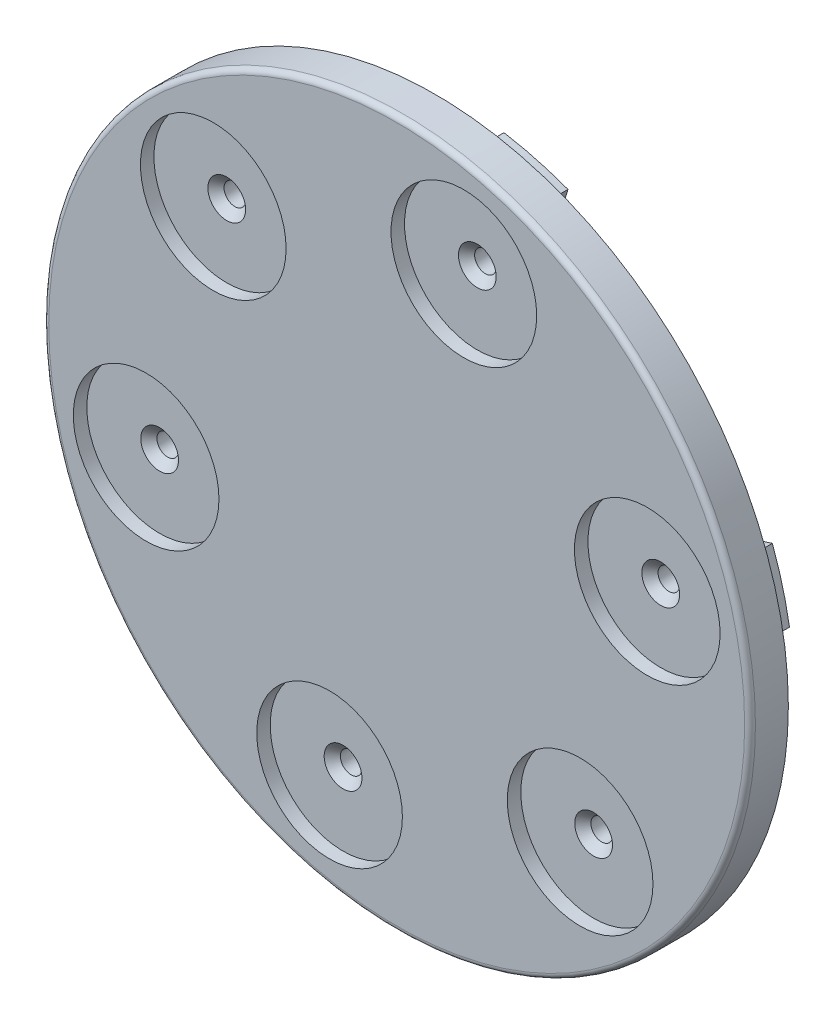
SolidWorks part; units mm, degrees
ref_plane "前视基准面" through (0, 0, 0) normal (0, 0, 1) x (1, 0, 0)
ref_plane "上视基准面" through (0, 0, 0) normal (0, 1, 0) x (1, 0, 0)
ref_plane "右视基准面" through (0, 0, 0) normal (1, 0, 0) x (0, 0, -1)
sketch "草图1" plane through (0, 0, 0) normal (0, 0, 1) x (1, 0, 0)
  line L0 (-32.5355, 8.7823) -> (-18.3435, 4.9515) construction
  line L1 (-30.451, 14.4369) -> (-16.7792, 10.7465)
  line L2 (-33.5795, 2.8469) -> (-19.9077, -0.8435)
  line L12 (10.6844, 63.6089) -> (3.9198, 33.4713)
  line L13 (-20.0302, 27.1013) -> (-41.0574, 49.7447)
  line L14 (-49.7447, 41.0574) -> (-27.0271, 20.1302)
  line L15 (-33.4855, -3.796) -> (-63.6089, -10.6844)
  line L16 (-60.4291, -22.5515) -> (-30.9468, -13.341)
  line L17 (-13.4553, -30.8973) -> (-22.5515, -60.4291)
  line L18 (-10.6844, -63.6089) -> (-3.9198, -33.4713)
  line L19 (20.0302, -27.1013) -> (41.0574, -49.7447)
  line L20 (49.7447, -41.0574) -> (27.0271, -20.1302)
  line L21 (33.4855, 3.796) -> (63.6089, 10.6844)
  line L22 (60.4291, 22.5515) -> (30.9468, 13.341)
  line L23 (13.4553, 30.8973) -> (22.5515, 60.4291)
  line L24 (10.6844, 63.6089) -> (3.9198, 33.4713)
  line L25 (-20.0302, 27.1013) -> (-41.0574, 49.7447)
  line L26 (-49.7447, 41.0574) -> (-27.0271, 20.1302)
  line L27 (-33.4855, -3.796) -> (-63.6089, -10.6844)
  line L28 (-60.4291, -22.5515) -> (-30.9468, -13.341)
  line L29 (-13.4553, -30.8973) -> (-22.5515, -60.4291)
  line L30 (-10.6844, -63.6089) -> (-3.9198, -33.4713)
  line L31 (20.0302, -27.1013) -> (41.0574, -49.7447)
  line L32 (49.7447, -41.0574) -> (27.0271, -20.1302)
  line L33 (33.4855, 3.796) -> (63.6089, 10.6844)
  line L34 (60.4291, 22.5515) -> (30.9468, 13.341)
  line L35 (13.4553, 30.8973) -> (22.5515, 60.4291)
  circle A0 centre (-34, 34) radius 1
  circle A1 centre (12.4449, 46.4449) radius 1
  circle A2 centre (46.4449, 12.4449) radius 1
  circle A3 centre (34, -34) radius 1
  circle A4 centre (-12.4449, -46.4449) radius 1
  circle A5 centre (-46.4449, -12.4449) radius 1
  arc A6 (-18.9727, -1.0179) -> (-15.8835, 10.4266) centre (0, 0) ccw
  arc A8 (-19.9077, -0.8435) -> (-18.9727, -1.0179) centre (-18.3435, 4.9515) ccw
  arc A9 (-33.5795, 2.8469) -> (-33.4855, -3.796) centre (0, 0) ccw
  arc A10 (-15.8835, 10.4266) -> (-16.7792, 10.7465) centre (-18.3435, 4.9515) ccw
  arc A12 (3.9198, 33.4713) -> (-20.0302, 27.1013) centre (0, 0) ccw
  arc A13 (-41.0574, 49.7447) -> (-49.7447, 41.0574) centre (0, 0) ccw
  arc A14 (-27.0271, 20.1302) -> (-33.4855, -3.796) centre (0, 0) ccw
  arc A15 (-63.6089, -10.6844) -> (-60.4291, -22.5515) centre (0, 0) ccw
  arc A16 (-30.9468, -13.341) -> (-13.4553, -30.8973) centre (0, 0) ccw
  arc A17 (-22.5515, -60.4291) -> (-10.6844, -63.6089) centre (0, 0) ccw
  arc A18 (-3.9198, -33.4713) -> (20.0302, -27.1013) centre (0, 0) ccw
  arc A19 (41.0574, -49.7447) -> (49.7447, -41.0574) centre (0, 0) ccw
  arc A20 (27.0271, -20.1302) -> (33.4855, 3.796) centre (0, 0) ccw
  arc A21 (63.6089, 10.6844) -> (60.4291, 22.5515) centre (0, 0) ccw
  arc A22 (30.9468, 13.341) -> (13.4553, 30.8973) centre (0, 0) ccw
  arc A23 (22.5515, 60.4291) -> (10.6844, 63.6089) centre (0, 0) ccw
  arc A24 (3.9198, 33.4713) -> (-20.0302, 27.1013) centre (0, 0) ccw
  arc A25 (-41.0574, 49.7447) -> (-49.7447, 41.0574) centre (0, 0) ccw
  arc A26 (-27.0271, 20.1302) -> (-30.451, 14.4369) centre (0, 0) ccw
  arc A27 (-63.6089, -10.6844) -> (-60.4291, -22.5515) centre (0, 0) ccw
  arc A28 (-30.9468, -13.341) -> (-13.4553, -30.8973) centre (0, 0) ccw
  arc A29 (-22.5515, -60.4291) -> (-10.6844, -63.6089) centre (0, 0) ccw
  arc A30 (-3.9198, -33.4713) -> (20.0302, -27.1013) centre (0, 0) ccw
  arc A31 (41.0574, -49.7447) -> (49.7447, -41.0574) centre (0, 0) ccw
  arc A32 (27.0271, -20.1302) -> (33.4855, 3.796) centre (0, 0) ccw
  arc A33 (63.6089, 10.6844) -> (60.4291, 22.5515) centre (0, 0) ccw
  arc A34 (30.9468, 13.341) -> (13.4553, 30.8973) centre (0, 0) ccw
  arc A35 (22.5515, 60.4291) -> (10.6844, 63.6089) centre (0, 0) ccw
  point P47 (0, 0)
  point P48 (-32.5355, 8.7823)
  dimension "D2" = 2
  dimension "D3" = 38
  dimension "D1" = 0
extrude "凸台-拉伸1" add sketch "草图1" along normal blind 9
sketch "草图2" plane through (0, 0, 9) normal (0, 0, 1) x (1, 0, 0)
  circle A0 centre (0, 0) radius 65.5
  arc A1 (-22.5515, -60.4291) -> (-10.6844, -63.6089) centre (0, 0) ccw construction
  dimension "D1" = 1
extrude "凸台-拉伸2" add sketch "草图2" against normal blind 1 and the other way blind 0.2
sketch "草图3" plane through (0, 0, 8) normal (0, 0, -1) x (-1, 0, 0)
  circle A0 centre (0, 0) radius 65.5
  circle A1 centre (0, 0) radius 63.5
  circle A2 centre (0, 0) radius 65.5 construction
  dimension "D1" = 2
  dimension "D2" = 0
extrude "凸台-拉伸3" add sketch "草图3" along normal blind 5.9
sketch "草图4" plane through (0, 0, 9.2) normal (0, 0, 1) x (1, 0, 0)
  circle A1 centre (46.4449, 12.4449) radius 14.5
  circle A6 centre (46.4449, 12.4449) radius 1
  circle A7 centre (34, -34) radius 14.5
  circle A8 centre (34, -34) radius 1
  circle A9 centre (-12.4449, -46.4449) radius 14.5
  circle A10 centre (-12.4449, -46.4449) radius 1
  circle A11 centre (-46.4449, -12.4449) radius 14.5
  circle A12 centre (-46.4449, -12.4449) radius 1
  circle A13 centre (-34, 34) radius 14.5
  circle A14 centre (-34, 34) radius 1
  circle A15 centre (12.4449, 46.4449) radius 14.5
  circle A16 centre (12.4449, 46.4449) radius 1
  point P21 (0, 0)
  dimension "D1" = 29
  dimension "D2" = 2
extrude "凸台-拉伸5" add sketch "草图4" against normal blind 4
sketch "草图6" plane through (0, 0, 9.2) normal (0, 0, 1) x (1, 0, 0)
  circle A0 centre (46.4449, 12.4449) radius 13.5
  circle A1 centre (34, -34) radius 13.5
  circle A2 centre (-12.4449, -46.4449) radius 13.5
  circle A3 centre (-46.4449, -12.4449) radius 13.5
  circle A4 centre (-34, 34) radius 13.5
  circle A5 centre (12.4449, 46.4449) radius 13.5
  point P16 (0, 0)
  dimension "D1" = 27
extrude "切除-拉伸1" cut sketch "草图6" against normal blind 2.5
sketch "草图7" plane through (0, 0, 6.7) normal (0, 0, 1) x (1, 0, 0)
  circle A1 centre (-34, 34) radius 2
  circle A2 centre (12.4449, 46.4449) radius 2
  circle A3 centre (46.4449, 12.4449) radius 2
  circle A4 centre (34, -34) radius 2
  circle A5 centre (-12.4449, -46.4449) radius 2
  circle A6 centre (-46.4449, -12.4449) radius 2
  point P15 (0, 0)
  dimension "D1" = 4
extrude "切除-拉伸2" cut sketch "草图7" against normal blind 4
chamfer "倒角1" distance 1.5 angle 45 6 edges at (48.4449, 12.4449, 6.7) (36, -34, 6.7) (-10.4449, -46.4449, 6.7) (-44.4449, -12.4449, 6.7) (-32, 34, 6.7) (14.4449, 46.4449, 6.7)
sketch "草图8" plane through (0, 0, 8) normal (0, 0, -1) x (-1, 0, 0)
  circle A0 centre (0, 0) radius 3.6
  circle A1 centre (0, 0) radius 6.6
extrude "凸台-拉伸6" add sketch "草图8" along normal up to vertex (6 mm away)
chamfer "倒角2" distance 3 angle 45 1 edges at (6.6, 0, 8)
chamfer "倒角3" distance 1 angle 45 1 edges at (-3.6, 0, 2)
sketch "草图9" plane through (0, 0, 2) normal (0, 0, -1) x (-1, 0, 0)
  line L0 (15.8835, 10.4266) -> (18.9727, -1.0179) construction
  line L1 (0, 0) -> (17.4281, 4.7044) construction
  line L2 (-0.4561, 1.6895) -> (16.972, 6.3939)
  line L3 (0.4561, -1.6895) -> (17.8842, 3.0149)
  arc A0 (-0.4561, 1.6895) -> (0.4561, -1.6895) centre (0, 0) ccw
  arc A1 (17.8842, 3.0149) -> (16.972, 6.3939) centre (17.4281, 4.7044) ccw
  point P7 (8.7141, 2.3522)
  dimension "D1" = 3.5
extrude "切除-拉伸3" cut sketch "草图9" against normal up to surface (6 mm away) up to face at (9.6, 0, 8)
fillet "圆角4" radius 1 1 edges at (6.3719, -1.72, 2)
fillet "圆角5" radius 1 12 edges at (42.121, 26.2852, 5.2) (49.6772, -1.6903, 5.2) (43.8242, -23.3353, 5.2) (23.3748, -43.8668, 5.2) (1.7031, -49.6205, 5.2) (-26.3024, -42.1766, 5.2) (-42.121, -26.2852, 5.2) (-49.6772, 1.6903, 5.2) (-43.8242, 23.3353, 5.2) (-23.3748, 43.8668, 5.2) (-1.7031, 49.6205, 5.2) (26.3024, 42.1766, 5.2)
fillet "圆角6" radius 1 1 edges at (65.5, 0, 9.2)
sketch "草图10" plane through (0, 0, 8) normal (0, 0, -1) x (-1, 0, 0)
  line L0 (30.451, 14.4369) -> (33.5795, 2.8469) construction
  line L1 (0.7939, 0.2143) -> (63.2367, 17.0695) construction
  line L3 (59.2714, 22.785) -> (62.686, 10.135)
  circle A0 centre (0, 0) radius 65.5 construction
  arc A3 (62.6324, -10.4611) -> (49.0081, 40.3789) centre (0, 0) ccw construction
  arc A4 (62.686, 10.135) -> (59.2714, 22.785) centre (0, 0) ccw
  point P9 (32.0153, 8.6419)
  point P12 (60.9787, 16.46)
  dimension "D1" = 90
  dimension "D2" = 30
extrude "凸台-拉伸7" add sketch "草图10" along normal up to surface (5.9 mm away) up to face at (-65.5, 0, 2.1)
sketch "草图11" plane through (-60.9787, 16.46, 0) normal (0.9654, -0.2606, 0) x (0, 0, -1)
  line L0 (-5.05, 6.5514) -> (-5.05, -6.5514) construction
  line L1 (-2.1, 6.5514) -> (-8, 6.5514) construction
  line L2 (-2.1, -6.5514) -> (-8, -6.5514) construction
  line L3 (-6.7453, 0) -> (-3.3547, 0) construction
  line L4 (-2.1, 6.5514) -> (-2.1, -6.5514) construction
  line L5 (-2.1, 0) -> (-8, 0) construction
  line L6 (-8, 6.5514) -> (-8, -6.5514) construction
  line L15 (-6.7453, 3.47) -> (-6.7453, -3.47)
  line L16 (-5.6253, -4.59) -> (-4.4747, -4.59)
  line L21 (-3.3547, -3.47) -> (-3.3547, 3.47)
  line L22 (-4.4747, 4.59) -> (-5.6253, 4.59)
  line L23 (-5.05, 4.59) -> (-5.05, -4.59) construction
  arc A12 (-6.7453, -3.47) -> (-5.6253, -4.59) centre (-5.6253, -3.47) ccw
  arc A13 (-4.4747, -4.59) -> (-3.3547, -3.47) centre (-4.4747, -3.47) ccw
  arc A14 (-3.3547, 3.47) -> (-4.4747, 4.59) centre (-4.4747, 3.47) ccw
  arc A15 (-5.6253, 4.59) -> (-6.7453, 3.47) centre (-5.6253, 3.47) ccw
  point P13 (-5.05, 0)
  point P29 (-5.05, 0)
extrude "切除-拉伸4" cut sketch "草图11" against normal blind 10
sketch "草图12" plane through (0, 0, 8) normal (0, 0, -1) x (-1, 0, 0)
  line L0 (59.2714, 22.785) -> (41.7968, 18.0681)
  line L1 (41.7968, 18.0681) -> (45.2114, 5.4181)
  line L2 (45.2114, 5.4181) -> (62.686, 10.135)
  line L3 (59.2714, 22.785) -> (62.686, 10.135) construction
  line L4 (59.2714, 22.785) -> (62.686, 10.135)
  dimension "D1" = 90
  dimension "D2" = 90
  dimension "D3" = 18.1
extrude "凸台-拉伸8" add sketch "草图12" along normal blind 0.25
fillet "圆角7" radius 0.2 16 edges at (-62.0215, 21.0613, 3.6009) (-63.2367, 17.0695, 3.3547) (-64.2298, 12.8365, 3.7763) (-64.2774, 12.5962, 5.05) (-64.1952, 13.0085, 6.4991) (-63.2367, 17.0695, 6.7453) (-61.9649, 21.2273, 6.3237) (-59.7825, 20.8914, 5.05) (-59.868, 20.5747, 3.6828) (-60.9787, 16.46, 3.3547) (-62.0893, 12.3453, 3.6828) (-62.1748, 12.0286, 5.05) (-62.0893, 12.3453, 6.4172) (-60.9787, 16.46, 6.7453) (-61.8851, 21.459, 5.05) (-59.868, 20.5747, 6.4172)
sketch "草图14" plane through (0, 0, 8) normal (0, 0, -1) x (-1, 0, 0)
  line L0 (41.7968, 18.0681) -> (45.2114, 5.4181) construction
  line L1 (41.7968, 18.0681) -> (43.2435, 12.7085)
  line L2 (45.2114, 5.4181) -> (43.6768, 5.0039)
  line L3 (42.4508, 5.7087) -> (39.5574, 16.4278)
  line L4 (40.2622, 17.6539) -> (41.7968, 18.0681)
  line L5 (43.7647, 10.7776) -> (45.2114, 5.4181)
  arc A0 (43.7647, 10.7776) -> (43.2435, 12.7085) centre (43.5041, 11.7431) ccw
  circle A1 centre (43.5041, 11.7431) radius 0.5
  arc A2 (43.6768, 5.0039) -> (42.4508, 5.7087) centre (43.4162, 5.9693) cw
  arc A3 (39.5574, 16.4278) -> (40.2622, 17.6539) centre (40.5228, 16.6884) cw
  point P16 (39.2968, 17.3933)
  dimension "D1" = 2
  dimension "D2" = 2.5
  dimension "D3" = 1
  dimension "D4" = 1
extrude "凸台-拉伸9" add sketch "草图14" along normal blind 3
fillet "圆角9" radius 1 11 edges at (-28.8797, 17.3682, 8) (-33.6966, -0.4769, 8) (-23.6151, 12.5917, 8) (-26.7436, 1.0017, 8) (-16.325, 10.6043, 8) (-19.4437, -0.9492, 8) (18.3435, -4.9515, 8) (-15.8835, 10.4266, 4) (-18.9727, -1.0179, 4) (-30.451, 14.4369, 4) (-33.5795, 2.8469, 4)
chamfer "倒角4" distance 1 angle 45 1 edges at (-41.0041, 11.0683, 8)
